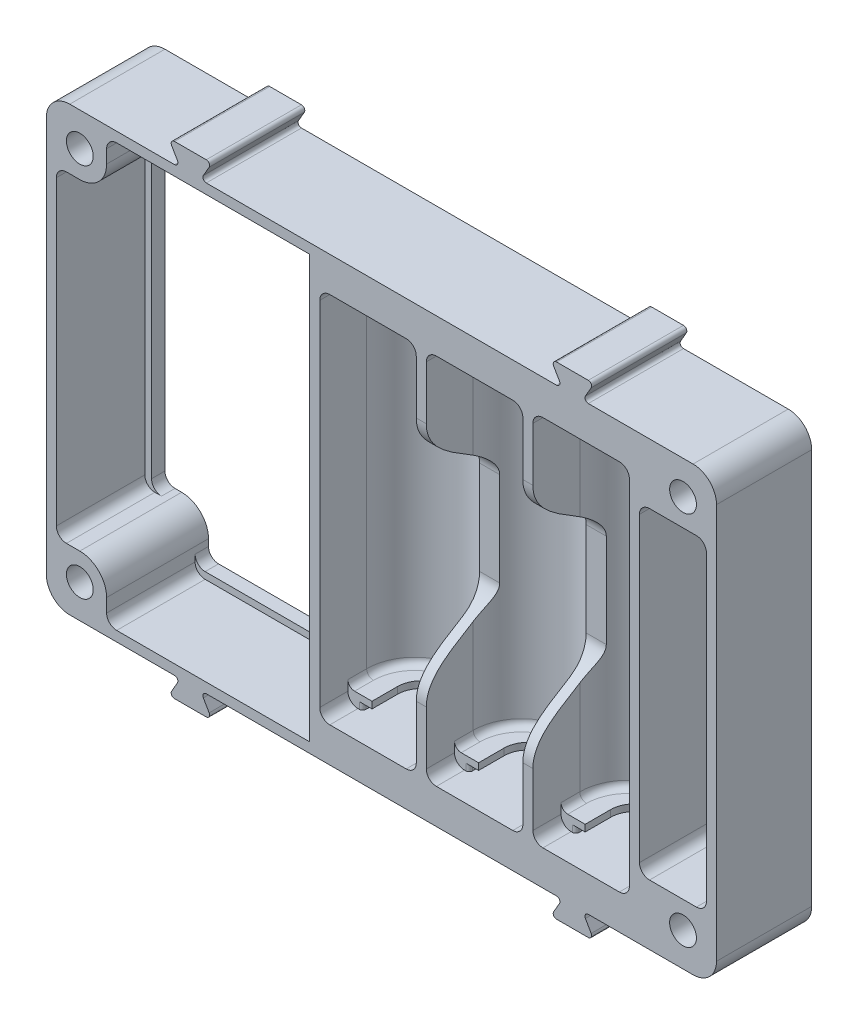
SolidWorks part; units mm, degrees
material "ABS"
ref_plane "Front Plane" through (0, 0, 0) normal (0, 0, 1) x (1, 0, 0)
ref_plane "Top Plane" through (0, 0, 0) normal (0, 1, 0) x (1, 0, 0)
ref_plane "Right Plane" through (0, 0, 0) normal (1, 0, 0) x (0, 0, -1)
sketch "Sketch1" plane through (0, 0, 0) normal (0, 1, 0) x (1, 0, 0)
  line L0 (-24.6, 0) -> (24.6, 0)
  line L1 (0, 0) -> (0, -8.2) construction
  line L2 (-5.4908, -1) -> (5.6475, -1) construction
  line L3 (7, -12.213) -> (7, -2.6204) construction
  line L4 (8.9, -12.0066) -> (8.9, -2.0587) construction
  line L5 (0, -8.2) -> (15.9, -8.2) construction
  line L6 (7.2, -8.2) -> (7.2, -15.2)
  line L7 (8.7, -8.2) -> (8.7, -15.2)
  line L8 (8.7, -15.2) -> (23.1, -15.2) construction
  line L9 (8.7, -15.2) -> (7.2, -15.2)
  line L10 (-1.7094, -15.2) -> (7.2, -15.2) construction
  line L11 (15.9, -8.2) -> (23.1, -8.2) construction
  line L12 (23.1, -15.2) -> (23.1, -8.2)
  line L13 (23.1, -15.2) -> (24.6, -15.2)
  line L14 (24.6, -15.2) -> (24.6, 0)
  line L15 (-24.6, -15.2) -> (-24.6, 0)
  line L16 (-23.1, -15.2) -> (-24.6, -15.2)
  line L17 (-23.1, -15.2) -> (-23.1, -8.2)
  line L18 (-8.7, -8.2) -> (-8.7, -15.2)
  line L19 (-8.7, -15.2) -> (-7.2, -15.2)
  line L20 (-7.2, -8.2) -> (-7.2, -15.2)
  circle A0 centre (0, -8.2) radius 7 construction
  arc A1 (-7.2, -8.2) -> (7.2, -8.2) centre (0, -8.2) cw
  circle A2 centre (15.9, -8.2) radius 7 construction
  arc A3 (8.7, -8.2) -> (23.1, -8.2) centre (15.9, -8.2) cw
  arc A4 (-8.7, -8.2) -> (-23.1, -8.2) centre (-15.9, -8.2) ccw
  dimension "D1" = 14
  dimension "D2" = 0.2
  dimension "D3" = 1
  dimension "D4" = 1.5
  dimension "D5" = 15.2
  dimension "D6" = 15.9
extrude "Boss-Extrude1" add sketch "Sketch1" along normal blind 27.8
sketch "Sketch2" plane through (0, 27.8, 0) normal (0, -1, 0) x (1, 0, 0)
  line L1 (-24.6, 15.2) -> (24.6, 15.2)
  line L2 (-24.6, 15.2) -> (-24.6, 0)
  line L3 (-24.6, 0) -> (24.6, 0)
  line L4 (24.6, 15.2) -> (24.6, 0)
extrude "Boss-Extrude2" add sketch "Sketch2" against normal blind 1.5
ref_plane "Plane1" through (-15.9, 0, 0) normal (1, 0, 0) x (0, 0, -1)
ref_plane "Plane3" through (15.9, 0, 0) normal (1, 0, 0) x (0, 0, -1)
sketch "Sketch6" plane through (0, 0, 0) normal (1, 0, 0) x (0, 0, -1)
  line L0 (-5, 0) -> (-15.2, 0)
  line L1 (-15.2, 0) -> (0, 0) construction
  line L2 (-15.2, 0) -> (-15.2, 18.3)
  line L3 (-15.2, 29.3) -> (-15.2, 0) construction
  line L4 (-5, 0) -> (-5, 7)
  line L5 (0, 29.3) -> (0, 0) construction
  line L6 (0, 29.3) -> (-15.2, 29.3) construction
  spline S0 degree 3 poles (-15.2, 18.3) (-15.2, 12.3) (-5, 11) (-5, 7) knots 0 0 0 0 1 1 1 1
  dimension "D4" = 12
  dimension "D5" = 18
  dimension "D1" = 7
  dimension "D2" = 5
  dimension "D3" = 11
extrude "Cut-Extrude2" cut sketch "Sketch6" against normal blind 15 and the other way blind 15
sketch "Sketch3" plane through (0, 27.8, 0) normal (0, -1, 0) x (1, 0, 0)
  line L0 (-10.4, 11) -> (-8.7, 11)
  line L1 (-8.7, 8.2) -> (-8.7, 15.2) construction
  line L2 (-8.7, 11) -> (-8.7, 0)
  line L3 (24.6, 0) -> (-24.6, 0) construction
  line L4 (-8.7, 0) -> (-23.1, 0)
  line L6 (-20.4, 2.9) -> (-11.4, 2.9)
  line L7 (-10.9, 3.4) -> (-10.9, 10.5)
  line L8 (-15.9, 15.2) -> (-15.9, 0) construction
  line L9 (-8.7, 15.2) -> (-23.1, 15.2) construction
  line L19 (-23.1, 11) -> (-23.1, 0)
  line L20 (-21.4, 11) -> (-23.1, 11)
  line L21 (-20.9, 3.4) -> (-20.9, 10.5)
  arc A1 (-11.4, 2.9) -> (-10.9, 3.4) centre (-11.4, 3.4) ccw
  arc A4 (-10.4, 11) -> (-10.9, 10.5) centre (-10.4, 10.5) ccw
  arc A6 (-20.4, 2.9) -> (-20.9, 3.4) centre (-20.4, 3.4) cw
  arc A7 (-21.4, 11) -> (-20.9, 10.5) centre (-21.4, 10.5) cw
  dimension "D6" = 0.5
  dimension "D7" = 0.5
  dimension "D1" = 5
  dimension "D2" = 11
  dimension "D3" = 2.9
extrude "Inner" add sketch "Sketch3" along normal blind 1
sketch "Sketch4" plane through (0, 26.8, 0) normal (0, -1, 0) x (1, 0, 0)
  line L1 (-8.7, 8.2) -> (-8.7, 15.2) construction
  line L2 (-8.7, 11) -> (-8.7, 0)
  line L3 (24.6, 0) -> (-24.6, 0) construction
  line L4 (-8.7, 0) -> (-23.1, 0)
  line L5 (-23.1, 0) -> (-23.1, 11)
  line L6 (-8.7, 11) -> (-10.4, 11) construction
  line L7 (-23.1, 11) -> (-19.5, 11)
  line L8 (-19.5, 11) -> (-19.5, 7.2)
  line L10 (-12.3, 7.2) -> (-12.3, 11)
  line L11 (-12.3, 11) -> (-8.7, 11)
  arc A0 (-19.5, 7.2) -> (-12.3, 7.2) centre (-15.9, 7.2) ccw
  dimension "D1" = 3.6
  dimension "D2" = 3.8
extrude "Boss-Extrude4" add sketch "Sketch4" along normal blind 1
sketch "Sketch5" plane through (0, 0, 15.2) normal (0, 0, 1) x (1, 0, 0)
  line L0 (-8.7, 27.8) -> (-23.1, 27.8) construction
  line L1 (-17.6, 27.8) -> (-14.2, 27.8)
  line L2 (-17.6, 27.8) -> (-17.6, 27.3)
  line L3 (-17.6, 27.3) -> (-14.2, 27.3)
  line L4 (-14.2, 27.8) -> (-14.2, 27.3)
  point P10 (-15.9, 27.8)
  dimension "D1" = 0.5
  dimension "D2" = 3.4
extrude "Cut-Extrude1" cut sketch "Sketch5" against normal through all
sketch "Sketch10" plane through (0, 0, 0) normal (0, 0, 1) x (1, 0, 0)
  line L0 (-24.6, 29.3) -> (24.6, 29.3) construction
  line L1 (-14.2, 27.3) -> (-17.6, 27.3)
  line L2 (-14.2, 27.3) -> (-14.2, 29.3)
  line L3 (-14.2, 29.3) -> (-17.6, 29.3)
  line L4 (-17.6, 27.3) -> (-17.6, 29.3)
extrude "Cut-Extrude6" cut sketch "Sketch10" along normal blind 0.6
mirror "Mirror1" about plane through (0, 0, 0) normal (1, 0, 0) of "Cut-Extrude6", "Inner", "Boss-Extrude4", "Cut-Extrude1"
ref_plane "Plane2" through (-7.95, 0, 0) normal (1, 0, 0) x (0, 0, -1)
mirror "Mirror2" about plane through (-7.95, 0, 0) normal (1, 0, 0) of "Cut-Extrude6", "Inner", "Boss-Extrude4", "Cut-Extrude1"
fillet "Fillet2" radius 1.5 6 edges at (-8.7, 27.8, 13.1) (-23.1, 27.8, 13.1) (8.7, 27.8, 13.1) (23.1, 27.8, 13.1) (7.2, 27.8, 13.1) (-7.2, 27.8, 13.1)
fillet "Fillet3" radius 1 9 edges at (-8.7, 25.8, 9.6) (-15.9, 25.8, 1) (-23.1, 25.8, 9.6) (23.1, 25.8, 9.6) (8.7, 25.8, 9.6) (7.2, 25.8, 9.6) (-7.2, 25.8, 9.6) (15.9, 25.8, 1) (0, 25.8, 1)
mirror "Mirror4" about plane through (0, 0, 0) normal (0, 1, 0) of bodies 108 110
sketch "Эскиз1" plane through (0, 0, 0) normal (0, 0, -1) x (-1, 0, 0)
  line L0 (-24.6, 29.3) -> (-24.6, -29.3) construction
  line L5 (-36.1, 33) -> (63.9, 33)
  line L6 (-36.1, 33) -> (-36.1, -33)
  line L7 (-36.1, -33) -> (63.9, -33)
  line L8 (63.9, 33) -> (63.9, -33)
  line L9 (-36.1, 33) -> (63.9, -33) construction
  line L10 (-36.1, -33) -> (63.9, 33) construction
  line L11 (-34.6, -31.5) -> (62.4, -31.5)
  line L12 (-34.6, -31.5) -> (-34.6, 31.5)
  line L13 (-34.6, 31.5) -> (62.4, 31.5)
  line L14 (62.4, -31.5) -> (62.4, 31.5)
  line L15 (-34.6, -31.5) -> (62.4, 31.5) construction
  line L16 (-34.6, 31.5) -> (62.4, -31.5) construction
  line L17 (24.6, 29.3) -> (24.6, -29.3) construction
  line L18 (-24.6, 29.3) -> (24.6, 29.3)
  line L19 (-24.6, 29.3) -> (-24.6, 31.5)
  line L20 (-24.6, 31.5) -> (24.6, 31.5)
  line L21 (24.6, 29.3) -> (24.6, 31.5)
  line L22 (-24.6, -29.3) -> (24.6, -29.3)
  line L23 (-24.6, -29.3) -> (-24.6, -31.5)
  line L24 (-24.6, -31.5) -> (24.6, -31.5)
  line L25 (24.6, -29.3) -> (24.6, -31.5)
  line L27 (-24.6, 29.3) -> (-24.6, -29.3) construction
  line L28 (62.4, 31.5) -> (54.9, 31.5)
  line L29 (62.4, 31.5) -> (62.4, 24)
  line L30 (62.4, 24) -> (54.9, 24)
  line L31 (54.9, 31.5) -> (54.9, 24)
  line L32 (62.4, -31.5) -> (54.9, -31.5)
  line L33 (62.4, -31.5) -> (62.4, -24)
  line L34 (62.4, -24) -> (54.9, -24)
  line L35 (54.9, -31.5) -> (54.9, -24)
  line L36 (-34.6, 31.5) -> (-24.6, 31.5)
  line L37 (-34.6, 31.5) -> (-34.6, 24)
  line L38 (-34.6, 24) -> (-24.6, 24)
  line L39 (-24.6, 31.5) -> (-24.6, 24)
  line L41 (-34.6, -31.5) -> (-24.6, -31.5)
  line L42 (-34.6, -31.5) -> (-34.6, -24)
  line L43 (-34.6, -24) -> (-24.6, -24)
  line L44 (-24.6, -31.5) -> (-24.6, -24)
  point P0 (13.9, 0)
  point P5 (13.9, 0)
  line M16 (24.6, 29.3) -> (17.6, 29.3)
  line M20 (14.2, 29.3) -> (1.7, 29.3)
  line M24 (-1.7, 29.3) -> (-14.2, 29.3)
  line M28 (-17.6, 29.3) -> (-24.6, 29.3)
  line M30 (-24.6, 29.3) -> (-24.6, -29.3)
  dimension "D1" = 100
  dimension "D2" = 66
  dimension "D3" = 1.5
  dimension "D4" = 1.5
  dimension "D5" = 10
  dimension "D6" = 7.5
extrude "Бобышка-Вытянуть1" add sketch "Эскиз1" against normal up to surface (15.2 mm away) contours L13 L31 L30 L14 | L35 L11 L14 L34 | L43 L12 L11 L23 M30 | L12 L38 L19 L13 M30 | L8 L5 L6 L7 L14 L11 L12 L13 | L21 L13 L19 L18 M16 M28 M24 M20 | L23 L22 L25 L24 region at (-13.9, 31.8018, 0) region at (29.6, -27.75, 0) region at (29.6, 27.75, 0) region at (-58.65, -27.75, 0) region at (0, 30.4, 0) region at (-58.65, 27.75, 0) up to face at (0, 0, 15.2)
sketch "Эскиз2" plane through (0, 0, 0) normal (0, 0, -1) x (-1, 0, 0)
  line L0 (62.4, -24) -> (62.4, 24) construction
  line L1 (-34.6, -31.5) -> (62.4, -31.5)
  line L2 (-34.6, -31.5) -> (-34.6, 31.5)
  line L3 (-34.6, 31.5) -> (62.4, 31.5)
  line L4 (62.4, -31.5) -> (62.4, 31.5)
  line L5 (-34.6, -24) -> (-34.6, 24) construction
  line L6 (24.6, 31.5) -> (54.9, 31.5) construction
  line L7 (24.6, -31.5) -> (54.9, -31.5) construction
  line L8 (-24.6, 24) -> (-24.6, -24) construction
  line L11 (-34.6, 24) -> (-24.6, 24)
  line L12 (-24.6, 31.5) -> (-24.6, 24)
  line L13 (54.9, 24) -> (62.4, 24)
  line L14 (54.9, 24) -> (54.9, 31.5)
  line L17 (54.9, -24) -> (62.4, -24)
  line L18 (54.9, -24) -> (54.9, -31.5)
  line L23 (-34.6, -24) -> (-24.6, -24)
  line L24 (-24.6, -31.5) -> (-24.6, -24)
  line L25 (-24.6, 30.5) -> (54.9, 30.5)
  line L26 (-24.6, -30.5) -> (54.9, -30.5)
  line L27 (-33.6, 24) -> (-33.6, -24)
  line L28 (61.4, -24) -> (61.4, 24)
  line L29 (62.4, 24) -> (54.9, 24) construction
  line M25 (-34.6, 24) -> (-24.6, 24)
  line M27 (-24.6, -24) -> (-34.6, -24)
  line M28 (-34.6, -24) -> (-34.6, 24)
  line M29 (24.6, -31.5) -> (24.6, 31.5)
  line M30 (24.6, 31.5) -> (54.9, 31.5)
  line M31 (54.9, 31.5) -> (54.9, 24)
  line M32 (54.9, 24) -> (62.4, 24)
  line M33 (62.4, 24) -> (62.4, -24)
  line M34 (62.4, -24) -> (54.9, -24)
  line M35 (54.9, -24) -> (54.9, -31.5)
  line M36 (54.9, -31.5) -> (24.6, -31.5)
  dimension "D1" = 1
  dimension "D2" = 1
  dimension "D3" = 1
  dimension "D4" = 1
extrude "Бобышка-Вытянуть2" add sketch "Эскиз2" against normal blind 2 contours L12 L3 L2 L11 M25 | L12 L25 L3 M29 | L25 M29 M31 M30 | L13 L4 L3 L14 M32 M31 | L28 L13 M34 M33 | L1 L4 L17 L18 M34 M35 | L26 L18 M29 M36 | L26 L24 L1 M29 | L1 L24 L23 L2 M27 | L27 L23 M25 M28 region at (29.6, -27.75, 0) region at (0, -31, 0) region at (34.1, 0, 0) region at (-39.75, -31, 0) region at (29.6, 27.75, 0) region at (-58.65, -27.75, 0) region at (-39.75, 31, 0) region at (0, 31, 0) region at (-61.9, 0, 0) region at (-58.65, 27.75, 0)
fillet "Скругление6" radius 3.5 4 edges at (36.1, 33, 7.6) (36.1, -33, 7.6) (-63.9, -33, 7.6) (-63.9, 33, 7.6)
sketch "Эскиз8" plane through (0, 0, 0) normal (0, 0, -1) x (-1, 0, 0)
  line L8 (62.4, -29.5) -> (62.4, 29.5)
  line L9 (-32.6, -31.5) -> (60.4, -31.5)
  line L10 (-34.6, 29.5) -> (-34.6, -29.5)
  line L11 (60.4, 31.5) -> (-32.6, 31.5)
  line L12 (62.4, -29.5) -> (62.4, 29.5)
  line L13 (-32.6, -31.5) -> (60.4, -31.5)
  line L14 (-34.6, 29.5) -> (-34.6, -29.5)
  line L15 (60.4, 31.5) -> (-32.6, 31.5)
  line L20 (63.9, -29.5) -> (63.9, 29.5)
  line L21 (-32.6, -33) -> (60.4, -33)
  line L22 (-36.1, 29.5) -> (-36.1, -29.5)
  line L23 (60.4, 33) -> (-32.6, 33)
  line L24 (63.9, -29.5) -> (63.9, 29.5)
  line L25 (-32.6, -33) -> (60.4, -33)
  line L26 (-36.1, 29.5) -> (-36.1, -29.5)
  line L27 (60.4, 33) -> (-32.6, 33)
  arc A8 (62.4, 29.5) -> (60.4, 31.5) centre (60.4, 29.5) ccw
  arc A9 (60.4, -31.5) -> (62.4, -29.5) centre (60.4, -29.5) ccw
  arc A10 (-34.6, -29.5) -> (-32.6, -31.5) centre (-32.6, -29.5) ccw
  arc A11 (-32.6, 31.5) -> (-34.6, 29.5) centre (-32.6, 29.5) ccw
  arc A12 (62.4, 29.5) -> (60.4, 31.5) centre (60.4, 29.5) ccw
  arc A13 (60.4, -31.5) -> (62.4, -29.5) centre (60.4, -29.5) ccw
  arc A14 (-34.6, -29.5) -> (-32.6, -31.5) centre (-32.6, -29.5) ccw
  arc A15 (-32.6, 31.5) -> (-34.6, 29.5) centre (-32.6, 29.5) ccw
  arc A20 (63.9, 29.5) -> (60.4, 33) centre (60.4, 29.5) ccw
  arc A21 (60.4, -33) -> (63.9, -29.5) centre (60.4, -29.5) ccw
  arc A22 (-36.1, -29.5) -> (-32.6, -33) centre (-32.6, -29.5) ccw
  arc A23 (-32.6, 33) -> (-36.1, 29.5) centre (-32.6, 29.5) ccw
  arc A24 (63.9, 29.5) -> (60.4, 33) centre (60.4, 29.5) ccw
  arc A25 (60.4, -33) -> (63.9, -29.5) centre (60.4, -29.5) ccw
  arc A26 (-36.1, -29.5) -> (-32.6, -33) centre (-32.6, -29.5) ccw
  arc A27 (-32.6, 33) -> (-36.1, 29.5) centre (-32.6, 29.5) ccw
  dimension "D1" = 1.5
  dimension "D2" = 0
extrude "Вырез-Вытянуть1" cut sketch "Эскиз8" against normal blind 1
fillet "Скругление7" radius 1.5 10 edges at (-24.6, -30.5, 1) (-54.9, -30.5, 1) (-24.6, 30.5, 1) (-54.9, 30.5, 1) (-61.4, 24, 1) (-61.4, -24, 1) (33.6, -24, 1) (24.6, -24, 7.6) (24.6, 24, 7.6) (33.6, 24, 1)
sketch "Эскиз11" plane through (0, 0, 15.2) normal (0, 0, 1) x (1, 0, 0)
  line L0 (-43.9, 33) -> (-45.6321, 36)
  line L2 (-45.6321, 36) -> (-39.1679, 36)
  line L3 (-39.1679, 36) -> (-40.9, 33)
  line L4 (-40.9, 33) -> (-43.9, 33)
  line L5 (13.1, 33) -> (11.3679, 36)
  line L6 (11.3679, 36) -> (17.8321, 36)
  line L7 (17.8321, 36) -> (16.1, 33)
  line L8 (16.1, 33) -> (13.1, 33)
  line L11 (-43.9, -33) -> (-45.6321, -36)
  line L13 (-45.6321, -36) -> (-39.1679, -36)
  line L14 (-39.1679, -36) -> (-40.9, -33)
  line L15 (-40.9, -33) -> (-43.9, -33)
  line L16 (13.1, -33) -> (11.3679, -36)
  line L17 (11.3679, -36) -> (17.8321, -36)
  line L18 (17.8321, -36) -> (16.1, -33)
  line L19 (16.1, -33) -> (13.1, -33)
  line L20 (-60.4, -33) -> (32.6, -33) construction
  line L21 (-60.4, 33) -> (32.6, 33) construction
  line L22 (-63.9, -29.5) -> (-63.9, 29.5) construction
  line L23 (36.1, -29.5) -> (36.1, 29.5) construction
  dimension "D1" = 60
  dimension "D2" = 3
  dimension "D3" = 3
  dimension "D4" = 3
  dimension "D5" = 20
  dimension "D6" = 20
  dimension "D7" = 3
extrude "Бобышка-Вытянуть3" add sketch "Эскиз11" against normal up to surface (14.2 mm away) up to face at (-13.9, 0, 1)
fillet "Скругление8" radius 0.5 16 edges at (-45.6321, -36, 8.1) (-43.9, -33, 8.1) (-39.1679, -36, 8.1) (-40.9, -33, 8.1) (17.8321, -36, 8.1) (16.1, -33, 8.1) (11.3679, -36, 8.1) (13.1, -33, 8.1) (16.1, 33, 8.1) (17.8321, 36, 8.1) (13.1, 33, 8.1) (11.3679, 36, 8.1) (-43.9, 33, 8.1) (-40.9, 33, 8.1) (-39.1679, 36, 8.1) (-45.6321, 36, 8.1)
fillet "Скругление9" radius 1.5 6 edges at (34.6, 24, 8.6) (34.6, -24, 8.6) (-54.9, 31.5, 8.6) (-62.4, 24, 8.6) (-62.4, -24, 8.6) (-54.9, -31.5, 8.6)
sketch "Эскиз3" plane through (0, 0, 15.2) normal (0, 0, 1) x (1, 0, 0)
  line L4 (-60.4, 33) -> (-44.766, 33) construction
  line L5 (-63.9, -29.5) -> (-63.9, 29.5) construction
  line L6 (36.1, -29.5) -> (36.1, 29.5) construction
  line L7 (-60.4, -33) -> (-44.766, -33) construction
  circle A0 centre (-58.9, 28) radius 2
  circle A1 centre (31.1, 28) radius 2
  circle A2 centre (31.1, -28) radius 2
  circle A3 centre (-58.9, -28) radius 2
  point P0 (-58.9, 28)
  point P1 (31.1, 28)
  point P2 (31.1, -28)
  point P3 (-58.9, -28)
  dimension "D5" = 4
  dimension "D1" = 5
  dimension "D2" = 5
  dimension "D3" = 5
  dimension "D4" = 5
sketch "Эскиз12" plane through (0, 0, 0) normal (0, 0, -1) x (-1, 0, 0)
  circle A0 centre (-31.1, 28) radius 2
  circle A1 centre (58.9, 28) radius 2
  circle A2 centre (58.9, -28) radius 2
  circle A3 centre (-31.1, -28) radius 2
  point P8 (58.9, 28)
  point P9 (58.9, -28)
  point P10 (-31.1, -28)
  point P12 (-31.1, 28)
  dimension "D1" = 4
extrude "Вырез-Вытянуть2" cut sketch "Эскиз12" against normal blind 4.2
extrude "Вырез-Вытянуть3" cut sketch "Эскиз3" against normal blind 4.2
fillet "Скругление10" radius 4 2 edges at (-54.9, 24, 7.6) (-54.9, -24, 7.6)
